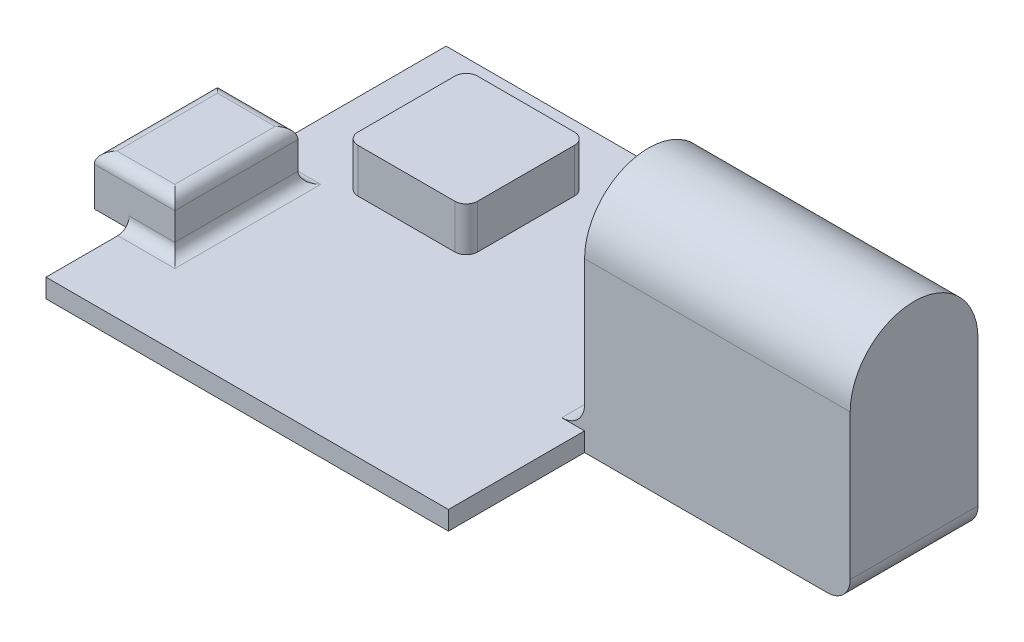
SolidWorks part; units mm, degrees
ref_plane "Front Plane" through (0, 0, 0) normal (0, 0, 1) x (1, 0, 0)
ref_plane "Top Plane" through (0, 0, 0) normal (0, 1, 0) x (1, 0, 0)
ref_plane "Right Plane" through (0, 0, 0) normal (1, 0, 0) x (0, 0, -1)
sketch "Sketch1" plane through (0, 0, 0) normal (0, 1, 0) x (1, 0, 0)
  line L1 (-17.65, 17.55) -> (17.65, 17.55)
  line L2 (-17.65, 17.55) -> (-17.65, -17.55)
  line L3 (-17.65, -17.55) -> (17.65, -17.55)
  line L4 (17.65, 17.55) -> (17.65, -17.55)
  line L5 (-17.65, 17.55) -> (17.65, -17.55) construction
  line L6 (-17.65, -17.55) -> (17.65, 17.55) construction
  line L7 (-11.13, 12.79) -> (-0.63, 12.79)
  line L8 (-11.13, 12.79) -> (-11.13, 2.29)
  line L9 (-11.13, 2.29) -> (-0.63, 2.29)
  line L10 (-0.63, 12.79) -> (-0.63, 2.29)
  line L11 (-11.13, 12.79) -> (-0.63, 2.29) construction
  line L12 (-11.13, 2.29) -> (-0.63, 12.79) construction
  line L13 (-13.65, 0.55) -> (-20.71, 0.55)
  line L14 (-13.65, 0.55) -> (-13.65, -10.25)
  line L15 (-13.65, -10.25) -> (-20.71, -10.25)
  line L16 (-20.71, 0.55) -> (-20.71, -10.25)
  point P0 (0, 0)
  point P6 (-6.7291, 6.6909)
  dimension "D1" = 35.1
  dimension "D2" = 35.3
  dimension "D3" = 10.5
  dimension "D4" = 10.8
  dimension "D5" = 7.3
  dimension "D6" = 4
  dimension "D7" = 3.06
  dimension "D8" = 4.76
  dimension "D9" = 6.52
extrude "Boss-Extrude1" add sketch "Sketch1" along normal blind 1.65 contours L14 L15 L2 L3 L4 L1 L13 L7 L10 L9 L8 | L15 L14 L13 L2 | L10 L7 L8 L9 region at (1.2199, 0, 0.5727) region at (-15.65, 0, 4.85) region at (-5.88, 0, -7.54)
extrude "Boss-Extrude2" add sketch "Sketch1<3>" along normal blind 4.4 from surface contours L15 L14 L13 L2 | L13 L16 L15 L2 region at (-15.65, 0, 4.85) region at (-19.18, 0, 4.85) starting at face at (0, 1.65, 0)
sketch "Sketch1<3>" plane through (0, 0, 0) normal (0, 1, 0) x (1, 0, 0) same geometry as "Sketch1"
extrude "Boss-Extrude3" add sketch "Sketch1<4>" along normal blind 3.86 from surface contours L10 L7 L8 L9 region at (-5.88, 0, -7.54) starting at face at (-7.825, 1.65, 2.425)
sketch "Sketch1<4>" plane through (0, 0, 0) normal (0, 1, 0) x (1, 0, 0) same geometry as "Sketch1"
fillet "Fillet1" radius 1 3 edges at (-13.65, 1.65, 4.85) (-15.65, 1.65, -0.55) (-15.65, 1.65, 10.25)
fillet "Fillet2" radius 1 4 edges at (-13.65, 6.05, 4.85) (-17.18, 6.05, 10.25) (-20.71, 6.05, 4.85) (-17.18, 6.05, -0.55)
sketch "Sketch2" plane through (-20.71, 0, 0) normal (-1, 0, 0) x (0, 0, 1)
  line L1 (1.0979, 2.9106) -> (8.8881, 2.9106)
  line L2 (1.0979, 2.9106) -> (1.0979, 4.2438)
  line L3 (1.0979, 4.2438) -> (8.8881, 4.2438)
  line L4 (8.8881, 2.9106) -> (8.8881, 4.2438)
extrude "Cut-Extrude1" cut sketch "Sketch2" against normal blind 2
fillet "Fillet3" radius 1 4 edges at (-11.13, 3.58, -12.79) (-0.63, 3.58, -12.79) (-0.63, 3.58, -2.29) (-11.13, 3.58, -2.29)
sketch "Sketch4" plane through (17.65, 0, 0) normal (1, 0, 0) x (0, 0, -1)
  line L0 (-5.605, 0) -> (-5.605, 14.7326)
  line L1 (17.55, 0) -> (-17.55, 0) construction
  line L2 (5.605, 14.7326) -> (5.605, 0)
  line L3 (5.605, 0) -> (-5.605, 0)
  arc A0 (-5.605, 14.7326) -> (5.605, 14.7326) centre (0, 14.7326) cw
  dimension "D1" = 20.3376
  dimension "D2" = 11.21
extrude "Boss-Extrude4" add sketch "Sketch4" along normal blind 23.3
fillet "Fillet4" radius 2 1 edges at (17.65, 1.65, 0)
fillet "Fillet5" radius 2 1 edges at (40.95, 0, 0)
